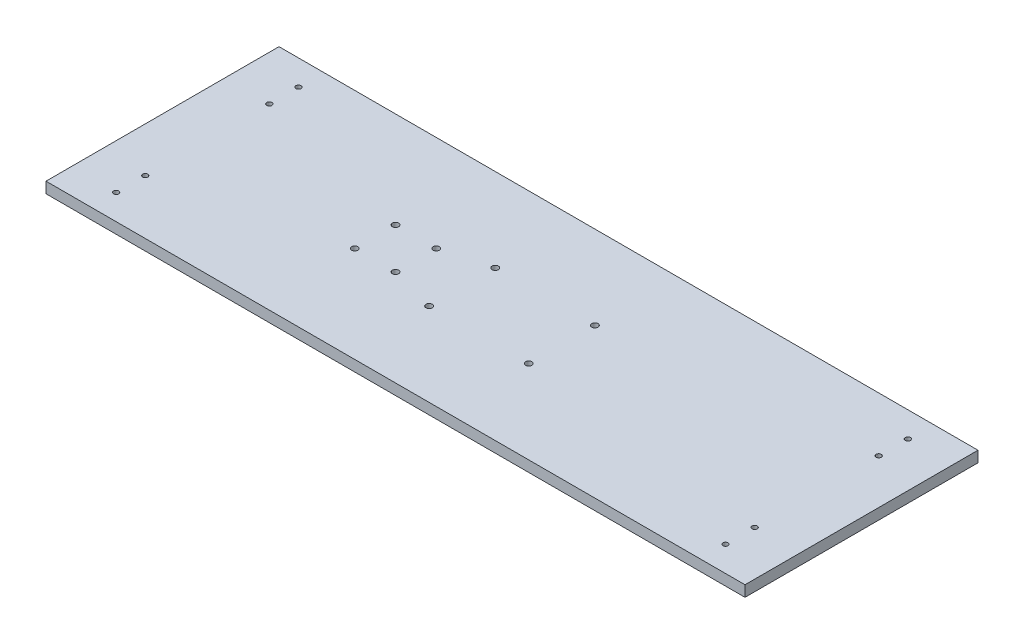
SolidWorks part; units mm, degrees
material "Pine"
ref_plane "Front Plane" through (0, 0, 0) normal (0, 0, 1) x (1, 0, 0)
ref_plane "Top Plane" through (0, 0, 0) normal (0, 1, 0) x (1, 0, 0)
ref_plane "Right Plane" through (0, 0, 0) normal (1, 0, 0) x (0, 0, -1)
sketch "Sketch1" plane through (0, 0, 0) normal (0, 1, 0) x (1, 0, 0)
  line L1 (0, 0) -> (609.6, 0)
  line L2 (0, 0) -> (0, 203.2)
  line L3 (0, 203.2) -> (609.6, 203.2)
  line L4 (609.6, 0) -> (609.6, 203.2)
  line L5 (304.8, 203.2) -> (304.8, 0) construction
  line L6 (0, 101.6) -> (609.6, 101.6) construction
  point P124 (304.8, 101.6)
  dimension "D1" = 609.6
  dimension "D2" = 203.2
extrude "Table Blank" add sketch "Sketch1" along normal blind 9.525
sketch "Table Location" plane through (0, 9.525, 0) normal (0, 1, 0) x (1, 0, 0)
  line L0 (0, 101.6) -> (609.6, 101.6) construction
  line L1 (228.6, 152.4) -> (381, 152.4) construction
  line L2 (228.6, 152.4) -> (228.6, 50.8) construction
  line L3 (228.6, 50.8) -> (381, 50.8) construction
  line L4 (381, 152.4) -> (381, 50.8) construction
  line L5 (304.8, 50.8) -> (304.8, 152.4) construction
  line L6 (228.6, 101.6) -> (381, 101.6) construction
  line L7 (304.8, 203.2) -> (304.8, 0) construction
  line L9 (261.366, 130.429) -> (348.234, 130.429) construction
  line L10 (261.366, 130.429) -> (261.366, 72.771) construction
  line L11 (261.366, 72.771) -> (348.234, 72.771) construction
  line L12 (348.234, 130.429) -> (348.234, 72.771) construction
  line L13 (304.8, 72.771) -> (304.8, 130.429) construction
  line L14 (261.366, 101.6) -> (348.234, 101.6) construction
  circle A0 centre (261.366, 72.771) radius 2.5 construction
  circle A1 centre (261.366, 130.429) radius 2.5 construction
  circle A2 centre (348.234, 130.429) radius 2.5 construction
  circle A3 centre (348.234, 72.771) radius 2.5 construction
  point P124 (304.8, 101.6)
  point P224 (304.8, 101.6)
  dimension "D1" = 152.4
  dimension "D2" = 101.6
  dimension "D3" = 86.868
  dimension "D4" = 57.658
hole_wizard "Table Holes (M5 Clearance)" positions "Sketch4" profile "Sketch5" hole size "M5" standard "ANSI Metric" end condition through all
sketch "Sketch4" plane through (0, 9.525, 0) normal (0, 1, 0) x (1, 0, 0)
  point P0 (261.366, 130.429)
  point P3 (348.234, 130.429)
  point P6 (348.234, 72.771)
  point P9 (261.366, 72.771)
sketch "Sketch5" plane through (261.366, 9.525, -130.429) normal (1, 0, 0) x (0, 0, 1)
  line L0 (0, 0) -> (0, 9.525)
  line L1 (0, 9.525) -> (2.75, 9.525)
  line L2 (2.75, 9.525) -> (2.75, 0)
  line L5 (2.75, 0) -> (0, 0)
  line L11 (0, -6.35) -> (0, 107.95) construction
  dimension "Thru Hole Dia." = 5.5
  dimension "Thru Hole Depth" = 9.525
sketch "Runner Location" plane through (0, 9.525, 0) normal (0, 1, 0) x (1, 0, 0)
  line L0 (0, 101.6) -> (609.6, 101.6) construction
  line L1 (177.8, 127) -> (228.6, 127) construction
  line L2 (177.8, 127) -> (177.8, 76.2) construction
  line L3 (177.8, 76.2) -> (228.6, 76.2) construction
  line L4 (228.6, 127) -> (228.6, 76.2) construction
  line L5 (203.2, 76.2) -> (203.2, 127) construction
  line L6 (177.8, 101.6) -> (228.6, 101.6) construction
  line L7 (228.6, 152.4) -> (228.6, 50.8) construction
  line L8 (185.42, 119.38) -> (185.42, 83.82) construction
  line L9 (185.42, 83.82) -> (220.98, 83.82) construction
  line L10 (220.98, 119.38) -> (220.98, 83.82) construction
  line L11 (185.42, 119.38) -> (220.98, 119.38) construction
  point P136 (203.2, 101.6)
  dimension "D1" = 50.8
  dimension "D2" = 7.62
hole_wizard "Runner Holes" positions "Sketch7" profile "Sketch8" hole size "M5" standard "ANSI Metric" end condition through all
sketch "Sketch7" plane through (0, 9.525, 0) normal (0, 1, 0) x (1, 0, 0)
  point P0 (185.42, 119.38)
  point P3 (220.98, 119.38)
  point P6 (220.98, 83.82)
  point P9 (185.42, 83.82)
sketch "Sketch8" plane through (185.42, 9.525, -119.38) normal (1, 0, 0) x (0, 0, 1)
  line L0 (0, 0) -> (0, 9.525)
  line L1 (0, 9.525) -> (2.75, 9.525)
  line L2 (2.75, 9.525) -> (2.75, 0)
  line L5 (2.75, 0) -> (0, 0)
  line L11 (0, -6.35) -> (0, 107.95) construction
  dimension "Thru Hole Dia." = 5.5
  dimension "Thru Hole Depth" = 9.525
sketch "Wheel Location" plane through (0, 9.525, 0) normal (0, 1, 0) x (1, 0, 0)
  line L0 (55.88, 187.452) -> (55.88, 15.748) construction
  line L1 (0, 101.6) -> (609.6, 101.6) construction
  line L2 (0, 0) -> (0, 203.2) construction
  line L3 (30.1879, 187.452) -> (45.4279, 187.452) construction
  line L4 (25.6921, 187.452) -> (30.1879, 187.452) construction
  line L5 (25.6921, 187.452) -> (25.6921, 15.748) construction
  line L6 (25.6921, 15.748) -> (30.1879, 15.748) construction
  line L7 (30.1879, 187.452) -> (30.1879, 15.748) construction
  line L8 (27.94, 15.748) -> (27.94, 187.452) construction
  line L9 (25.6921, 101.6) -> (30.1879, 101.6) construction
  line L10 (30.1879, 15.748) -> (45.4279, 15.748) construction
  line L11 (30.1879, 15.748) -> (30.1879, 53.848) construction
  line L12 (30.1879, 53.848) -> (45.4279, 53.848) construction
  line L13 (45.4279, 15.748) -> (45.4279, 53.848) construction
  line L14 (45.4279, 187.452) -> (45.4279, 149.352) construction
  line L15 (30.1879, 149.352) -> (45.4279, 149.352) construction
  point P2 (55.88, 101.6)
  point P11 (39.0779, 22.098)
  point P16 (39.0779, 47.498)
  point P17 (39.0779, 181.102)
  point P18 (39.0779, 155.702)
  point P487 (27.94, 101.6)
  dimension "D1" = 171.704
  dimension "D2" = 55.88
  dimension "D3" = 4.4958
  dimension "D4" = 27.94
  dimension "D5" = 6.35
  dimension "D7" = 15.24
  dimension "D8" = 38.1
  dimension "D6" = 6.35
  dimension "D9" = 25.4
hole_wizard "Wheel Holes (M4 Clearance)" positions "Sketch10" profile "Sketch11" hole size "M4" standard "ANSI Metric" end condition through all
sketch "Sketch10" plane through (0, 9.525, 0) normal (0, 1, 0) x (1, 0, 0)
  point P0 (39.0779, 181.102)
  point P3 (39.0779, 155.702)
  point P6 (39.0779, 47.498)
  point P9 (39.0779, 22.098)
sketch "Sketch11" plane through (39.0779, 9.525, -181.102) normal (1, 0, 0) x (0, 0, 1)
  line L0 (0, 0) -> (0, 9.525)
  line L1 (0, 9.525) -> (2.25, 9.525)
  line L2 (2.25, 9.525) -> (2.25, 0)
  line L5 (2.25, 0) -> (0, 0)
  line L11 (0, -6.35) -> (0, 107.95) construction
  dimension "Thru Hole Dia." = 4.5
  dimension "Thru Hole Depth" = 9.525
ref_plane "Plane1" through (304.8, 0, 0) normal (-1, 0, 0) x (0, 0, 1)
mirror "Mirror1" about plane through (304.8, 0, 0) normal (-1, 0, 0) of "Wheel Holes (M4 Clearance)"
equation "\"baseplate x\"= 24"
equation "\"baseplate y\"= 8"
equation "\"D1@Sketch1\"=\"baseplate x\""
equation "\"D2@Sketch1\"=\"baseplate y\""
equation "\"stock thick\"= 3 / 8"
equation "\"D1@Table Blank\" = \"stock thick\""
equation "\"table x\"= 6"
equation "\"table y\"= 4"
equation "\"D1@Table Location\" = \"table x\""
equation "\"D2@Table Location\" = \"table y\""
equation "\"width wheelmount\"= 6.76"
equation "\"offset wheelmount\"= 2.2"
equation "\"D2@Wheel Location\" = \"offset wheelmount\""
equation "\"D1@Wheel Location\" = \"width wheelmount\""
equation "\"D4@Wheel Location\" = \"D2@Wheel Location\" / 2"
